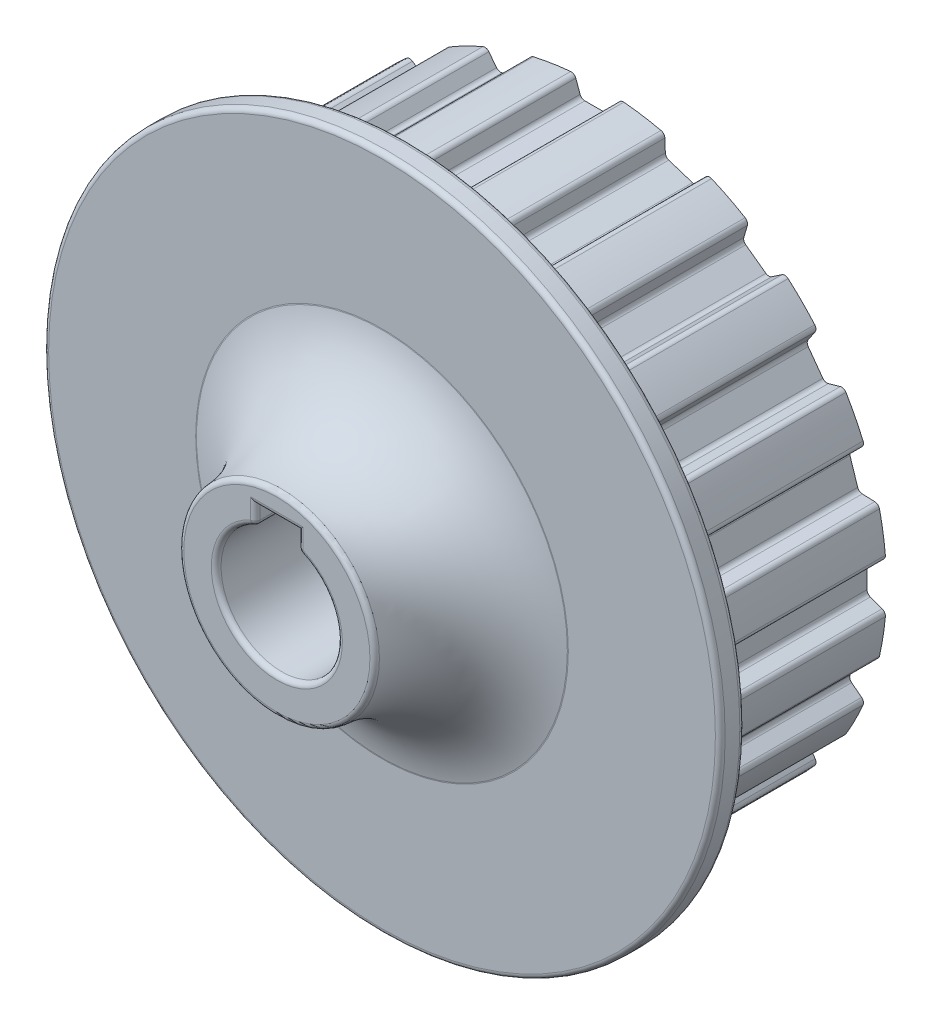
SolidWorks part; units mm, degrees
ref_plane "Front Plane" through (0, 0, 0) normal (0, 0, 1) x (1, 0, 0)
ref_plane "Top Plane" through (0, 0, 0) normal (0, 1, 0) x (1, 0, 0)
ref_plane "Right Plane" through (0, 0, 0) normal (1, 0, 0) x (0, 0, -1)
sketch "Sketch1" plane through (0, 0, 0) normal (0, 1, 0) x (1, 0, 0)
  line L0 (0, 36.1296) -> (0, -19.4741) construction
sketch "Sketch7" plane through (0, 0, 0) normal (0, 0, 1) x (1, 0, 0)
  line L0 (0, 0) -> (0, 28.5291) construction
  line L1 (-2.325, 29.4841) -> (-2.9401, 31.1741) construction
  line L2 (-2.325, 29.4841) -> (-1.6298, 27.5741) construction
  line L3 (-1.6298, 27.5741) -> (1.6298, 27.5741) construction
  line L4 (1.6298, 27.5741) -> (2.325, 29.4841) construction
  line L5 (2.325, 29.4841) -> (-2.325, 29.4841) construction
  line L6 (0, 27.5741) -> (0, 29.4841) construction
  line L7 (2.325, 29.4841) -> (2.9401, 31.1741) construction
  line L8 (-2.9401, 31.1741) -> (2.9401, 31.1741) construction
  line L9 (0, 0) -> (8.816, 27.1328) construction
  line L10 (8.816, 27.1328) -> (9.1394, 28.1281) construction
  line L11 (0, 29.4841) -> (0, 29.5757) construction
  line L12 (0, 29.5757) -> (0, 31.3125) construction
  line L13 (0, 30.4441) -> (9.4077, 28.954) construction
  line L14 (9.1394, 28.1281) -> (9.6761, 29.7799) construction
  circle A1 centre (0, 0) radius 28.5291 construction
  circle A2 centre (-1.2727, 28.0841) radius 0.51 construction
  circle A3 centre (1.2727, 28.0841) radius 0.51 construction
  circle A4 centre (0, 0) radius 29.5757
  circle A5 centre (0, 0) radius 31.3125 construction
  dimension "D3" = 40
  dimension "D6" = 1.02
  dimension "D1" = 3.6
  dimension "D2" = 18
  dimension "D7" = 9.525
  dimension "D4" = 1.91
  dimension "D5" = 4.65
extrude "Boss-Extrude1" add sketch "Sketch7" along normal blind 7.25 and the other way blind 7.25 contours A4 region at (0, 0, 0)
sketch "Sketch14" plane through (0, 0, 0) normal (1, 0, 0) x (0, 0, -1)
  line L0 (-18, 0) -> (-18, 10)
  line L1 (-18, 0) -> (0, 0)
  line L2 (0, 0) -> (0, 19)
  line L3 (0, 19) -> (-7.25, 19)
  line L4 (-7.25, 19) -> (-18, 10)
  line L5 (-7.25, 29.5757) -> (-7.25, -29.5757) construction
  line L6 (-18, 6.7395) -> (-3.3555, 19) construction
  arc A0 (-7.25, 19) -> (-18, 10) centre (-18.1316, 21.0773) cw
  dimension "D1" = 10
  dimension "D2" = 19
  dimension "D3" = 18
  dimension "D4" = 2.5
revolve "Revolve1" add sketch "Sketch14" angle 360 about L0 region at (0, 7.5733, 7.5341) region at (0, 9.2725, 16.1663) region at (0, 17.2765, 6.6188)
sketch "Sketch9" plane through (0, 0, 0) normal (0, 0, 1) x (1, 0, 0)
  line L0 (2, 0) -> (-2, 0) construction
  line L1 (-2, 0) -> (-2, 7.5) construction
  line L2 (-2, 7.5) -> (2, 7.5) construction
  line L3 (2, 7.5) -> (2, 0) construction
  circle A0 centre (0, 0) radius 6 construction
  dimension "D1" = 12
  dimension "D2" = 4
  dimension "D3" = 7.5
sketch "Sketch10" plane through (0, 0, 0) normal (0, 0, 1) x (1, 0, 0)
  line L0 (2, 0) -> (-2, 0) construction
  line L1 (-2.2, 7.7) -> (2.2, 7.7)
  line L2 (-2.2, 7.7) -> (-2.2, 0)
  line L3 (-2.2, 0) -> (2.2, 0)
  line L4 (2.2, 7.7) -> (2.2, 0)
  line L5 (-2, 7.5) -> (2, 7.5) construction
  line L6 (2, 7.5) -> (2, 0) construction
  circle A0 centre (0, 0) radius 6.2
  circle A1 centre (0, 0) radius 6 construction
  dimension "D1" = 0.2
  dimension "D2" = 0.2
  dimension "D3" = 0.2
extrude "Cut-Extrude3" cut sketch "Sketch10" against normal through all both and the other way through all contours A0 L4 L1 L2 | L2 A0 L4 L3 | L4 A0 L2 L3 region at (0, 6.8793, 0) region at (0, 3.0348, 0) region at (0, -0.8613, 0)
sketch "Sketch11" [suppressed] plane through (0, 0, 0) normal (0, 1, 0) x (1, 0, 0)
  line L0 (29.5757, 7.25) -> (-29.5757, 7.25) construction
  line L1 (11, 7.25) -> (17.5, 7.25)
  line L2 (11, 7.25) -> (11, 4.75)
  line L3 (11, 4.75) -> (17.5, 4.75)
  line L4 (17.5, 7.25) -> (17.5, 4.75)
  line L5 (-29.5757, -7.25) -> (29.5757, -7.25) construction
  line L6 (11, -7.25) -> (17.5, -7.25)
  line L7 (11, -7.25) -> (11, -4.75)
  line L8 (11, -4.75) -> (17.5, -4.75)
  line L9 (17.5, -7.25) -> (17.5, -4.75)
  line L11 (11, 4.75) -> (11, -4.75) construction
  line L12 (17.5, -4.75) -> (17.5, 4.75) construction
  line L13 (6.2, 7.25) -> (-6.2, 7.25) construction
  line L14 (0, 7.25) -> (22.5, 7.25)
  line L15 (0, 7.25) -> (0, -7.25)
  line L16 (0, -7.25) -> (22.5, -7.25)
  line L17 (22.5, 7.25) -> (22.5, -7.25)
  line L18 (-6.2, -7.25) -> (6.2, -7.25) construction
  line L19 (6, 7.25) -> (6, -7.25) construction
  dimension "D1" = 22.5
  dimension "D2" = 6
  dimension "D3" = 5
  dimension "D4" = 5
  dimension "D5" = 2.5
sketch "Sketch15" plane through (0, 0, -7.25) normal (0, 0, -1) x (-1, 0, 0)
  circle A0 centre (0, 0) radius 8.0081
  circle A1 centre (0, 0) radius 2.25
  dimension "D1" = 4.5
extrude "Boss-Extrude2" add sketch "Sketch15" against normal blind 5.5
sketch "Sketch16" plane through (0, 0, -7.25) normal (0, 0, -1) x (-1, 0, 0)
  circle A0 centre (0, 0) radius 5
  dimension "D1" = 10
extrude "Cut-Extrude4" cut sketch "Sketch16" against normal blind 3
sketch "Sketch17" plane through (0, 0, -7.25) normal (0, 0, -1) x (-1, 0, 0)
  circle A0 centre (0, 0) radius 29.5757
  circle A1 centre (0, 0) radius 29.5757 construction
  circle A2 centre (0, 0) radius 5
  circle A3 centre (0, 0) radius 5 construction
extrude "Boss-Extrude3" add sketch "Sketch17" along normal blind 7.5
sketch "Sketch8" plane through (0, 0, 0) normal (0, 0, 1) x (1, 0, 0)
  line L6 (-1.6298, 27.5741) -> (-2.3583, 29.5757)
  line L7 (-2.3583, 29.5757) -> (2.3583, 29.5757)
  line L8 (2.3583, 29.5757) -> (1.6298, 27.5741)
  line L9 (1.6298, 27.5741) -> (-1.6298, 27.5741)
  line L10 (-2.325, 29.4841) -> (-1.6298, 27.5741) construction
  line L11 (1.6298, 27.5741) -> (2.325, 29.4841) construction
  line L12 (6.9708, 26.7282) -> (6.8965, 28.8569)
  line L13 (6.8965, 28.8569) -> (11.3823, 27.3994)
  line L14 (11.3823, 27.3994) -> (10.0709, 25.7209)
  line L15 (10.0709, 25.7209) -> (6.9708, 26.7282)
  line L16 (14.8891, 23.2659) -> (15.4762, 25.3134)
  line L17 (15.4762, 25.3134) -> (19.292, 22.541)
  line L18 (19.292, 22.541) -> (17.5262, 21.35)
  line L19 (17.5262, 21.35) -> (14.8891, 23.2659)
  line L20 (21.35, 17.5262) -> (22.541, 19.292)
  line L21 (22.541, 19.292) -> (25.3134, 15.4762)
  line L22 (25.3134, 15.4762) -> (23.2659, 14.8891)
  line L23 (23.2659, 14.8891) -> (21.35, 17.5262)
  line L24 (25.7209, 10.0709) -> (27.3994, 11.3823)
  line L25 (27.3994, 11.3823) -> (28.8569, 6.8965)
  line L26 (28.8569, 6.8965) -> (26.7282, 6.9708)
  line L27 (26.7282, 6.9708) -> (25.7209, 10.0709)
  line L28 (27.5741, 1.6298) -> (29.5757, 2.3583)
  line L29 (29.5757, 2.3583) -> (29.5757, -2.3583)
  line L30 (29.5757, -2.3583) -> (27.5741, -1.6298)
  line L31 (27.5741, -1.6298) -> (27.5741, 1.6298)
  line L32 (26.7282, -6.9708) -> (28.8569, -6.8965)
  line L33 (28.8569, -6.8965) -> (27.3994, -11.3823)
  line L34 (27.3994, -11.3823) -> (25.7209, -10.0709)
  line L35 (25.7209, -10.0709) -> (26.7282, -6.9708)
  line L36 (23.2659, -14.8891) -> (25.3134, -15.4762)
  line L37 (25.3134, -15.4762) -> (22.541, -19.292)
  line L38 (22.541, -19.292) -> (21.35, -17.5262)
  line L39 (21.35, -17.5262) -> (23.2659, -14.8891)
  line L40 (17.5262, -21.35) -> (19.292, -22.541)
  line L41 (19.292, -22.541) -> (15.4762, -25.3134)
  line L42 (15.4762, -25.3134) -> (14.8891, -23.2659)
  line L43 (14.8891, -23.2659) -> (17.5262, -21.35)
  line L44 (10.0709, -25.7209) -> (11.3823, -27.3994)
  line L45 (11.3823, -27.3994) -> (6.8965, -28.8569)
  line L46 (6.8965, -28.8569) -> (6.9708, -26.7282)
  line L47 (6.9708, -26.7282) -> (10.0709, -25.7209)
  line L48 (1.6298, -27.5741) -> (2.3583, -29.5757)
  line L49 (2.3583, -29.5757) -> (-2.3583, -29.5757)
  line L50 (-2.3583, -29.5757) -> (-1.6298, -27.5741)
  line L51 (-1.6298, -27.5741) -> (1.6298, -27.5741)
  line L52 (-6.9708, -26.7282) -> (-6.8965, -28.8569)
  line L53 (-6.8965, -28.8569) -> (-11.3823, -27.3994)
  line L54 (-11.3823, -27.3994) -> (-10.0709, -25.7209)
  line L55 (-10.0709, -25.7209) -> (-6.9708, -26.7282)
  line L56 (-14.8891, -23.2659) -> (-15.4762, -25.3134)
  line L57 (-15.4762, -25.3134) -> (-19.292, -22.541)
  line L58 (-19.292, -22.541) -> (-17.5262, -21.35)
  line L59 (-17.5262, -21.35) -> (-14.8891, -23.2659)
  line L60 (-21.35, -17.5262) -> (-22.541, -19.292)
  line L61 (-22.541, -19.292) -> (-25.3134, -15.4762)
  line L62 (-25.3134, -15.4762) -> (-23.2659, -14.8891)
  line L63 (-23.2659, -14.8891) -> (-21.35, -17.5262)
  line L64 (-25.7209, -10.0709) -> (-27.3994, -11.3823)
  line L65 (-27.3994, -11.3823) -> (-28.8569, -6.8965)
  line L66 (-28.8569, -6.8965) -> (-26.7282, -6.9708)
  line L67 (-26.7282, -6.9708) -> (-25.7209, -10.0709)
  line L68 (-27.5741, -1.6298) -> (-29.5757, -2.3583)
  line L69 (-29.5757, -2.3583) -> (-29.5757, 2.3583)
  line L70 (-29.5757, 2.3583) -> (-27.5741, 1.6298)
  line L71 (-27.5741, 1.6298) -> (-27.5741, -1.6298)
  line L72 (-26.7282, 6.9708) -> (-28.8569, 6.8965)
  line L73 (-28.8569, 6.8965) -> (-27.3994, 11.3823)
  line L74 (-27.3994, 11.3823) -> (-25.7209, 10.0709)
  line L75 (-25.7209, 10.0709) -> (-26.7282, 6.9708)
  line L76 (-23.2659, 14.8891) -> (-25.3134, 15.4762)
  line L77 (-25.3134, 15.4762) -> (-22.541, 19.292)
  line L78 (-22.541, 19.292) -> (-21.35, 17.5262)
  line L79 (-21.35, 17.5262) -> (-23.2659, 14.8891)
  line L80 (-17.5262, 21.35) -> (-19.292, 22.541)
  line L81 (-19.292, 22.541) -> (-15.4762, 25.3134)
  line L82 (-15.4762, 25.3134) -> (-14.8891, 23.2659)
  line L83 (-14.8891, 23.2659) -> (-17.5262, 21.35)
  line L84 (-10.0709, 25.7209) -> (-11.3823, 27.3994)
  line L85 (-11.3823, 27.3994) -> (-6.8965, 28.8569)
  line L86 (-6.8965, 28.8569) -> (-6.9708, 26.7282)
  line L87 (-6.9708, 26.7282) -> (-10.0709, 25.7209)
  circle A0 centre (0, 0) radius 29.5757 construction
  point P119 (0, 0)
  dimension "D1" = 20
extrude "Cut-Extrude2" cut sketch "Sketch8" against normal through all both and the other way through all
fillet "Fillet2" radius 0.51 80 edges at (-28.7595, -6.8999, -3.75) (-27.3226, -11.3223, -3.75) (-25.2198, -15.4494, -3.75) (-22.4866, -19.2113, -3.75) (-19.2113, -22.4866, -3.75) (-15.4494, -25.2198, -3.75) (-11.3223, -27.3226, -3.75) (-6.8999, -28.7595, -3.75) (-2.325, -29.4841, -3.75) (2.325, -29.4841, -3.75) (6.8999, -28.7595, -3.75) (11.3223, -27.3226, -3.75) (15.4494, -25.2198, -3.75) (19.2113, -22.4866, -3.75) (22.4866, -19.2113, -3.75) (25.2198, -15.4494, -3.75) (27.3226, -11.3223, -3.75) (28.7595, -6.8999, -3.75) (29.4841, -2.325, -3.75) (29.4841, 2.325, -3.75) (28.7595, 6.8999, -3.75) (27.3226, 11.3223, -3.75) (25.2198, 15.4494, -3.75) (22.4866, 19.2113, -3.75) (19.2113, 22.4866, -3.75) (15.4494, 25.2198, -3.75) (11.3223, 27.3226, -3.75) (6.8999, 28.7595, -3.75) (2.325, 29.4841, -3.75) (-26.7282, -6.9708, -3.75) (-25.7209, -10.0709, -3.75) (-23.2659, -14.8891, -3.75) (-21.35, -17.5262, -3.75) (-17.5262, -21.35, -3.75) (-14.8891, -23.2659, -3.75) (-10.0709, -25.7209, -3.75) (-6.9708, -26.7282, -3.75) (-1.6298, -27.5741, -3.75) (1.6298, -27.5741, -3.75) (6.9708, -26.7282, -3.75) (10.0709, -25.7209, -3.75) (14.8891, -23.2659, -3.75) (17.5262, -21.35, -3.75) (21.35, -17.5262, -3.75) (23.2659, -14.8891, -3.75) (25.7209, -10.0709, -3.75) (26.7282, -6.9708, -3.75) (27.5741, -1.6298, -3.75) (27.5741, 1.6298, -3.75) (26.7282, 6.9708, -3.75) (25.7209, 10.0709, -3.75) (23.2659, 14.8891, -3.75) (21.35, 17.5262, -3.75) (17.5262, 21.35, -3.75) (14.8891, 23.2659, -3.75) (10.0709, 25.7209, -3.75) (6.9708, 26.7282, -3.75) (1.6298, 27.5741, -3.75) (-1.6298, 27.5741, -3.75) (-2.325, 29.4841, -3.75) (-6.8999, 28.7595, -3.75) (-6.9708, 26.7282, -3.75) (-10.0709, 25.7209, -3.75) (-11.3223, 27.3226, -3.75) (-15.4494, 25.2198, -3.75) (-14.8891, 23.2659, -3.75) (-17.5262, 21.35, -3.75) (-19.2113, 22.4866, -3.75) (-22.4866, 19.2113, -3.75) (-21.35, 17.5262, -3.75) (-23.2659, 14.8891, -3.75) (-25.2198, 15.4494, -3.75) (-27.3226, 11.3223, -3.75) (-25.7209, 10.0709, -3.75) (-26.7282, 6.9708, -3.75) (-28.7595, 6.8999, -3.75) (-29.4841, 2.325, -3.75) (-27.5741, 1.6298, -3.75) (-27.5741, -1.6298, -3.75) (-29.4841, -2.325, -3.75)
sketch "Sketch18" plane through (0, 0, -14.75) normal (0, 0, -1) x (-1, 0, 0)
  circle A0 centre (0, 0) radius 5
  circle A1 centre (0, 0) radius 34.5757
  circle A2 centre (0, 0) radius 29.5757
  circle A3 centre (0, 0) radius 5 construction
  circle A4 centre (0, 0) radius 29.5757 construction
  dimension "D1" = 5
extrude "Boss-Extrude4" add sketch "Sketch18" along normal blind 2.5 contours A1 A2 | A2 A0 region at (33.5977, 0, -14.75) region at (28.7391, 0, -14.75)
sketch "Sketch19" plane through (0, 0, 7.25) normal (0, 0, 1) x (1, 0, 0)
  circle A0 centre (0, 0) radius 19
  circle A1 centre (0, 0) radius 34.5757
  circle A2 centre (0, 0) radius 34.5757 construction
  circle A3 centre (0, 0) radius 19 construction
extrude "Boss-Extrude5" add sketch "Sketch19" against normal blind 2.5
sketch "Sketch20" plane through (0, 0, 18) normal (0, 0, 1) x (1, 0, 0)
  line L0 (-2.2, 5.7966) -> (-2.2, 7.7)
  line L1 (-2.2, 7.7) -> (2.2, 7.7)
  line L2 (-2.2, 7.7) -> (2.2, 7.7) construction
  line L3 (2.2, 7.7) -> (2.2, 5.7966)
  circle A0 centre (0, 0) radius 6.2
  arc A1 (-2.2, 5.7966) -> (2.2, 5.7966) centre (0, 0) ccw construction
  arc M2 (2.2, 5.7966) -> (-2.2, 5.7966) centre (0, 0) cw
  line M3 (-2.2, 5.7966) -> (-2.2, 7.7)
  line M4 (-2.2, 7.7) -> (2.2, 7.7)
  line M5 (2.2, 7.7) -> (2.2, 5.7966)
extrude "Cut-Extrude5" cut sketch "Sketch20" against normal through all contours A0 M5 M4 M3 | A0 M2 region at (0, 6.8793, 18) region at (0, 0, 18)
fillet "Fillet3" radius 0.5 12 edges at (2.2, 5.7966, 0.375) (-2.2, 5.7966, 0.375) (2.2, 6.7483, 18) (-2.2, 6.7483, 18) (0, 7.7, 18) (-19, 0, 7.25) (-10, 0, 18) (0, -6.2, 18) (34.5757, 0, 4.75) (-34.5757, 0, -14.75) (-34.5757, 0, -17.25) (34.5757, 0, 7.25)
ref_plane "Plane1" through (0, 0, -5.25) normal (0, 0, 1) x (1, 0, 0)
sketch "Sketch21" plane through (0, 0, -5.25) normal (0, 0, 1) x (1, 0, 0)
  circle A0 centre (0, 0) radius 8.0081
  circle A1 centre (0, 0) radius 2.25
  circle A2 centre (0, 0) radius 6.2
  arc A3 (-2.4985, 5.6743) -> (2.4985, 5.6743) centre (0, 0) ccw construction
  dimension "D1" = 4.5
extrude "Boss-Extrude6" add sketch "Sketch21" against normal blind 2.5 contours A2 A1 | A0 A2 region at (-7.7816, 0, -5.25) region at (-6.0246, 0, -5.25)
extrude "Boss-Extrude7" add sketch "Sketch21<4>" against normal up to surface (12 mm away) contours A0 A2 region at (-7.7816, 0, -5.25) up to face at (-34.0757, 0, -17.25)
sketch "Sketch21<4>" plane through (0, 0, -5.25) normal (0, 0, 1) x (1, 0, 0) same geometry as "Sketch21"
sketch "Sketch23" plane through (0, 0, -14.75) normal (0, 0, 1) x (1, 0, 0)
  line L0 (0, 27.5741) -> (0, 6.2) construction
  line L2 (1.2727, 27.5741) -> (-1.2727, 27.5741) construction
  circle A0 centre (0, 0) radius 16.8871 construction
  circle A1 centre (0, 0) radius 6.2 construction
  circle A2 centre (0, -16.8871) radius 1.75
  circle A3 centre (-14.6246, 8.4435) radius 1.75
  circle A4 centre (14.6246, 8.4435) radius 1.75
  point P10 (0, 16.8871)
  point P19 (0, 0)
  point P26 (0, 0)
  dimension "D1" = 3.5
  dimension "D2" = 3
extrude "Cut-Extrude7" cut sketch "Sketch23" along normal blind 10 and the other way through all
ref_plane "Plane2" through (0, 0, -12.25) normal (0, 0, 1) x (1, 0, 0)
sketch "Sketch24" plane through (0, 0, -12.25) normal (0, 0, 1) x (1, 0, 0)
  line L0 (0, -16.8871) -> (0, 0) construction
  line L1 (-14.6246, 5.0949) -> (-11.7246, 6.7692)
  line L2 (-11.7246, 6.7692) -> (-11.7246, 10.1178)
  line L3 (-11.7246, 10.1178) -> (-14.6246, 11.7922)
  line L4 (-14.6246, 11.7922) -> (-17.5246, 10.1178)
  line L5 (-17.5246, 10.1178) -> (-17.5246, 6.7692)
  line L6 (-17.5246, 6.7692) -> (-14.6246, 5.0949)
  line L7 (2.9, -18.5614) -> (2.9, -15.2127)
  line L8 (2.9, -15.2127) -> (0, -13.5384)
  line L9 (0, -13.5384) -> (-2.9, -15.2127)
  line L10 (-2.9, -15.2127) -> (-2.9, -18.5614)
  line L11 (-2.9, -18.5614) -> (0, -20.2357)
  line L12 (0, -20.2357) -> (2.9, -18.5614)
  line L13 (14.6246, 5.0949) -> (17.5246, 6.7692)
  line L14 (17.5246, 6.7692) -> (17.5246, 10.1178)
  line L15 (17.5246, 10.1178) -> (14.6246, 11.7922)
  line L16 (14.6246, 11.7922) -> (11.7246, 10.1178)
  line L17 (11.7246, 10.1178) -> (11.7246, 6.7692)
  line L18 (11.7246, 6.7692) -> (14.6246, 5.0949)
  line L19 (0, 0) -> (14.6246, 8.4435) construction
  line L21 (-14.6246, 8.4435) -> (0, 0) construction
  circle A0 centre (-14.6246, 8.4435) radius 2.9 construction
  circle A1 centre (0, -16.8871) radius 2.9 construction
  circle A2 centre (14.6246, 8.4435) radius 2.9 construction
  dimension "D1" = 5.8
extrude "Cut-Extrude8" cut sketch "Sketch24" along normal blind 3 contours L13 L14 L15 L16 | L13 L16 L17 L18 | L3 L4 L5 L6 | L3 L6 L1 L2 | L10 L7 L8 L9 | L10 L11 L12 L7 region at (-14.6246, 8.4435, -12.25) region at (0, -16.8871, -12.25) region at (14.6246, 8.4435, -12.25)
sketch "Sketch25" plane through (0, 0, -9.25) normal (0, 0, -1) x (-1, 0, 0)
  circle A0 centre (0, -16.8871) radius 1.75
  circle A1 centre (14.6246, 8.4435) radius 1.75
  circle A2 centre (-14.6246, 8.4435) radius 1.75
  circle A3 centre (0, -16.8871) radius 1.75 construction
extrude "Boss-Extrude8" add sketch "Sketch25" against normal blind 0.2
sketch "Sketch22" plane through (0, 0, 0) normal (0, 1, 0) x (1, 0, 0)
  line L0 (34.5757, 15.25) -> (34.5757, 16.75) construction
  line L1 (-34.5757, 17.25) -> (34.5757, 17.25)
  line L2 (-34.5757, 17.25) -> (-34.5757, 14.75)
  line L3 (-34.5757, 14.75) -> (34.5757, 14.75)
  line L4 (34.5757, 17.25) -> (34.5757, 14.75)
  line L5 (-34.5757, 17.25) -> (34.5757, 14.75) construction
  line L6 (-34.5757, 14.75) -> (34.5757, 17.25) construction
  line L7 (-32.1547, -18) -> (32.1547, -18) construction
  line L8 (-34.5757, 14.75) -> (34.5757, 14.75)
  line L9 (-34.5757, 14.75) -> (-34.5757, -18)
  line L10 (-34.5757, -18) -> (34.5757, -18)
  line L11 (34.5757, 14.75) -> (34.5757, -18)
  line L12 (-34.0757, 14.75) -> (34.0757, 14.75) construction
  line L13 (1.75, 17.25) -> (-1.75, 17.25) construction
  line L14 (-34.5757, 16.75) -> (-34.5757, 15.25) construction
  point P0 (0, 16)
extrude "Cut-Extrude10" cut sketch "Sketch22" against normal through all both and the other way through all contours L4 L1 L2 L3 region at (0, 0, -16)
